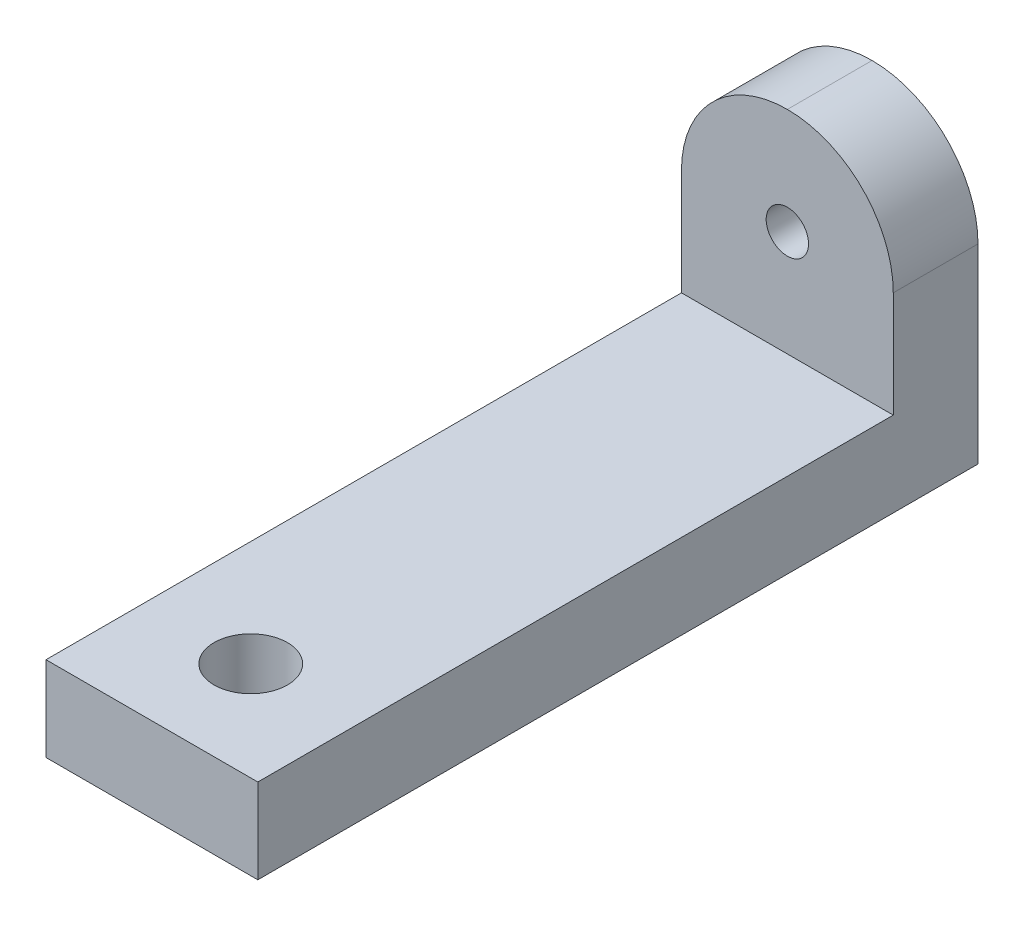
SolidWorks part; units mm, degrees
ref_plane "Front Plane" through (0, 0, 0) normal (0, 0, 1) x (1, 0, 0)
ref_plane "Top Plane" through (0, 0, 0) normal (0, 1, 0) x (1, 0, 0)
ref_plane "Right Plane" through (0, 0, 0) normal (1, 0, 0) x (0, 0, -1)
sketch "Sketch1" plane through (0, 0, 0) normal (1, 0, 0) x (0, 0, -1)
  line L1 (0, 0) -> (51, 0)
  line L2 (0, 0) -> (0, 6)
  line L3 (0, 6) -> (45, 6)
  line L4 (51, 0) -> (51, 3.9167)
  line L6 (51, 3.9167) -> (51, 21)
  line L7 (51, 21) -> (45, 21)
  line L8 (45, 6) -> (45, 21)
  dimension "D1" = 51
  dimension "D2" = 6
  dimension "D3" = 6
  dimension "D4" = 15
extrude "Boss-Extrude1" add sketch "Sketch1" along normal blind 15
sketch "Sketch2" plane through (0, 6, 0) normal (0, 1, 0) x (1, 0, 0)
  line L0 (15, 0) -> (0, 0) construction
  line L1 (15, 45) -> (15, 0) construction
  circle A0 centre (7.5, 7) radius 2.6
  dimension "D1" = 5.2
  dimension "D2" = 7
  dimension "D3" = 7.5
extrude "Cut-Extrude1" cut sketch "Sketch2" against normal through all
sketch "Sketch3" plane through (0, 0, -45) normal (0, 0, 1) x (1, 0, 0)
  line L0 (15, 21) -> (0, 21) construction
  line L1 (15, 21) -> (15, 6) construction
  circle A0 centre (7.5, 13.5) radius 1.5
  dimension "D1" = 3
  dimension "D2" = 7.5
  dimension "D3" = 7.5
extrude "Cut-Extrude2" cut sketch "Sketch3" against normal through all
fillet "Fillet1" radius 7.5 2 edges at (0, 21, -48) (15, 21, -48)
